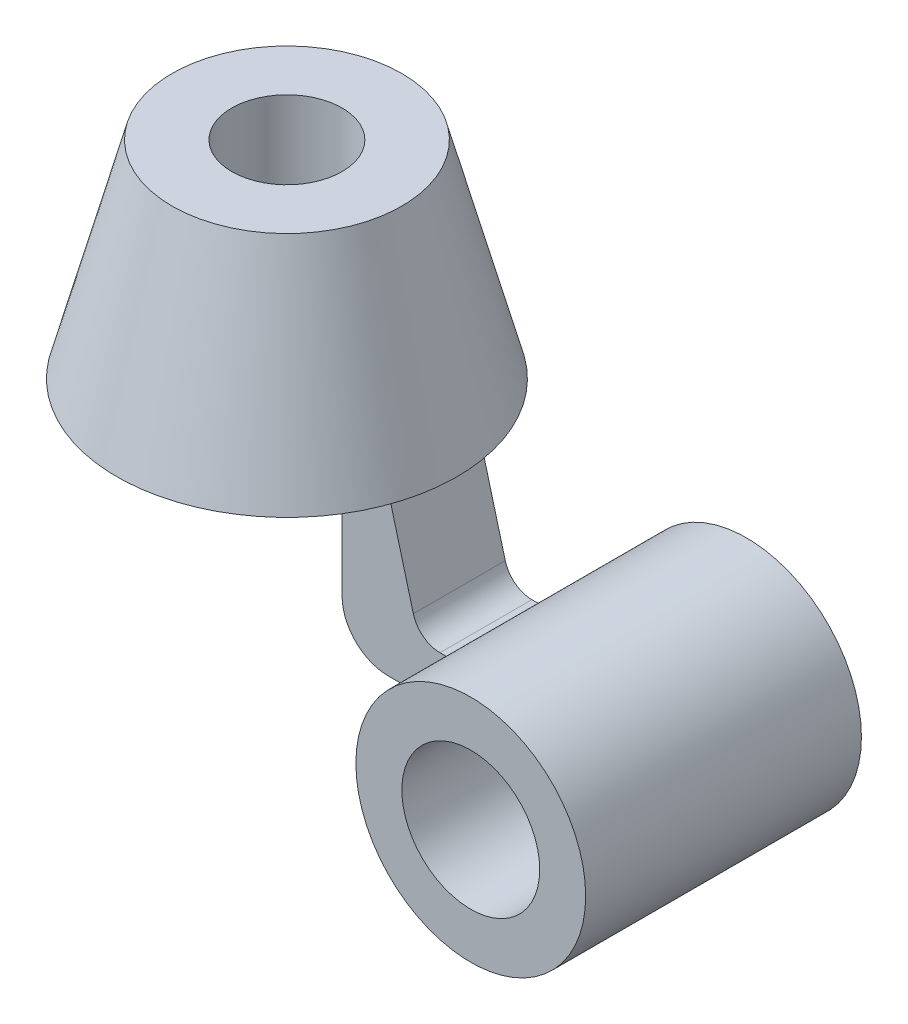
SolidWorks part; units mm, degrees
ref_plane "Front Plane" through (0, 0, 0) normal (0, 0, 1) x (1, 0, 0)
ref_plane "Top Plane" through (0, 0, 0) normal (0, 1, 0) x (1, 0, 0)
ref_plane "Right Plane" through (0, 0, 0) normal (1, 0, 0) x (0, 0, -1)
sketch "Sketch1" plane through (0, 0, 0) normal (0, 0, 1) x (1, 0, 0)
  line L0 (0, 0) -> (0, 45)
  line L1 (0, 45) -> (25, 45)
  line L2 (25, 45) -> (37, 0)
  line L3 (37, 0) -> (0, 0)
  dimension "D1" = 37
  dimension "D2" = 45
  dimension "D3" = 25
revolve "Revolve1" add sketch "Sketch1" angle 360 about L0
sketch "Sketch2" plane through (0, 0, 0) normal (0, 0, 1) x (1, 0, 0)
  circle A0 centre (70, -35) radius 25
  dimension "D3" = 50
  dimension "D1" = 70
  dimension "D2" = 35
extrude "Boss-Extrude1" add sketch "Sketch2" along normal blind 30 and the other way blind 30 separate body
sketch "Sketch3" plane through (0, 0, 0) normal (0, 0, 1) x (1, 0, 0)
  line L0 (22, 0) -> (22, -35)
  line L1 (-37, 0) -> (37, 0) construction
  line L2 (22, -35) -> (74.4739, -35)
  line L3 (74.4739, -35) -> (74.4739, -25)
  line L4 (74.4739, -25) -> (38.6987, -25)
  line L5 (38.6987, -25) -> (32, 0)
  line L6 (32, 0) -> (22, 0)
  dimension "D1" = 22
  dimension "D2" = 10
  dimension "D3" = 10
  dimension "D4" = 15
  dimension "D5" = 35
extrude "Boss-Extrude2" add sketch "Sketch3" along normal blind 10 and the other way blind 10
fillet "Fillet1" radius 10 1 edges at (22, -35, 0)
fillet "Fillet2" radius 6 1 edges at (38.6987, -25, 0)
sketch "Sketch4" plane through (0, 45, 0) normal (0, 1, 0) x (1, 0, 0)
  point P0 (0, 0)
hole_wizard "Ø1.0mm Dowel Hole1" positions "Sketch4" profile "Sketch5" hole size "Ø1.0" standard "ISO" end condition through all
sketch "Sketch5" plane through (0, 45, 0) normal (1, 0, 0) x (0, 0, 1)
  line L0 (0, 0) -> (0, 105)
  line L1 (0, 105) -> (12, 105)
  line L2 (12, 105) -> (12, 0)
  line L5 (12, 0) -> (0, 0)
  line L11 (0, -6.35) -> (0, 107.95) construction
  dimension "Thru Hole Dia." = 24
  dimension "Thru Hole Depth" = 105
sketch "Sketch6" plane through (0, 0, 30) normal (0, 0, 1) x (1, 0, 0)
  point P0 (70, -35)
hole_wizard "Ø1.0mm Dowel Hole2" positions "Sketch6" profile "Sketch7" hole size "Ø1.0" standard "ISO" end condition through all
sketch "Sketch7" plane through (70, -35, 30) normal (1, 0, 0) x (0, -1, 0)
  line L0 (0, 0) -> (0, 67)
  line L1 (0, 67) -> (15, 67)
  line L2 (15, 67) -> (15, 0)
  line L5 (15, 0) -> (0, 0)
  line L11 (0, -6.35) -> (0, 107.95) construction
  dimension "Thru Hole Dia." = 30
  dimension "Thru Hole Depth" = 67
